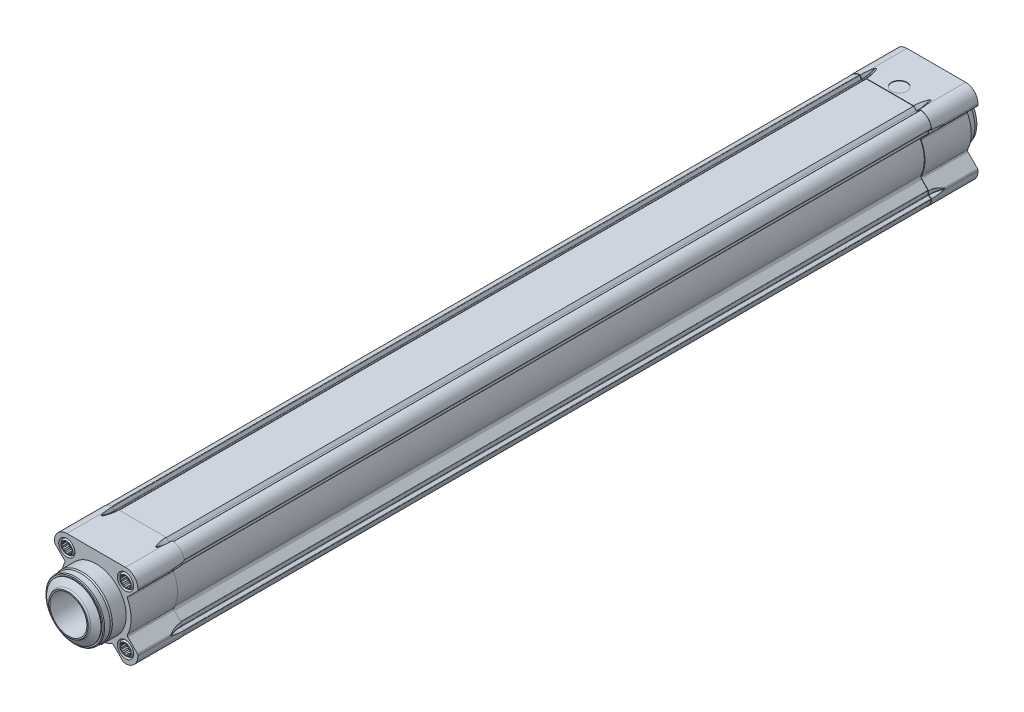
SolidWorks part; units mm, degrees
ref_plane "Front Plane" through (0, 0, 0) normal (0, 0, 1) x (1, 0, 0)
ref_plane "Top Plane" through (0, 0, 0) normal (0, 1, 0) x (1, 0, 0)
ref_plane "Right Plane" through (0, 0, 0) normal (1, 0, 0) x (0, 0, -1)
ref_plane "Plane1" through (0, 0, -30) normal (0, 0, 1) x (1, 0, 0)
sketch "Sketch1" plane through (0, 0, -30) normal (0, 0, 1) x (1, 0, 0)
  line L0 (-26.7071, 17.5147) -> (-20.4561, 11.2637)
  line L1 (-20.4561, -11.2637) -> (-26.7071, -17.5147)
  line L2 (-27, -18.2218) -> (-27, -19)
  line L3 (-19, -27) -> (-18.2218, -27)
  line L4 (-17.5147, -26.7071) -> (-11.2637, -20.4561)
  line L5 (11.2637, -20.4561) -> (17.5147, -26.7071)
  line L6 (18.2218, -27) -> (19, -27)
  line L7 (27, -19) -> (27, -18.2218)
  line L8 (26.7071, -17.5147) -> (20.4561, -11.2637)
  line L9 (20.4561, 11.2637) -> (26.7071, 17.5147)
  line L10 (27, 18.2218) -> (27, 19)
  line L11 (19, 27) -> (-19, 27)
  line L12 (-27, 19) -> (-27, 18.2218)
  arc A0 (-27, 18.2218) -> (-26.7071, 17.5147) centre (-26, 18.2218) ccw
  arc A1 (-20.4561, 11.2637) -> (-20.2683, 10.1102) centre (-21.1632, 10.5566) cw
  arc A2 (-20.2683, 10.1102) -> (-20.2683, -10.1102) centre (0, 0) ccw
  arc A3 (-20.2683, -10.1102) -> (-20.4561, -11.2637) centre (-21.1632, -10.5566) cw
  arc A4 (-26.7071, -17.5147) -> (-27, -18.2218) centre (-26, -18.2218) ccw
  arc A5 (-27, -19) -> (-19, -27) centre (-19, -19) ccw
  arc A6 (-18.2218, -27) -> (-17.5147, -26.7071) centre (-18.2218, -26) ccw
  arc A7 (-11.2637, -20.4561) -> (-10.1102, -20.2683) centre (-10.5566, -21.1632) cw
  arc A8 (-10.1102, -20.2683) -> (10.1102, -20.2683) centre (0, 0) ccw
  arc A9 (10.1102, -20.2683) -> (11.2637, -20.4561) centre (10.5566, -21.1632) cw
  arc A10 (17.5147, -26.7071) -> (18.2218, -27) centre (18.2218, -26) ccw
  arc A11 (19, -27) -> (27, -19) centre (19, -19) ccw
  arc A12 (27, -18.2218) -> (26.7071, -17.5147) centre (26, -18.2218) ccw
  arc A13 (20.4561, -11.2637) -> (20.2683, -10.1102) centre (21.1632, -10.5566) cw
  arc A14 (20.2683, -10.1102) -> (20.2683, 10.1102) centre (0, 0) ccw
  arc A15 (20.2683, 10.1102) -> (20.4561, 11.2637) centre (21.1632, 10.5566) cw
  arc A16 (26.7071, 17.5147) -> (27, 18.2218) centre (26, 18.2218) ccw
  arc A17 (27, 19) -> (19, 27) centre (19, 19) ccw
  arc A18 (-19, 27) -> (-27, 19) centre (-19, 19) ccw
extrude "Boss-Extrude1" add sketch "Sketch1" along normal blind 30
sketch "Sketch2" plane through (0, 0, -30) normal (0, 0, 1) x (1, 0, 0)
  line L0 (-19.3, 33.75) -> (-19.3, 27)
  line L1 (-19.3, 27) -> (-18.203, 25.1)
  line L2 (-18.0298, 25) -> (-17.3281, 25)
  line L3 (-17.1867, 25.0586) -> (-15.2453, 27)
  line L4 (-15.2453, 27) -> (15.2453, 27)
  line L5 (15.2453, 27) -> (17.1867, 25.0586)
  line L6 (17.3281, 25) -> (18.0298, 25)
  line L7 (18.203, 25.1) -> (19.3, 27)
  line L8 (19.3, 27) -> (19.3, 33.75)
  line L9 (19.3, 33.75) -> (-19.3, 33.75)
  line L10 (-50, 45) -> (50, 45) construction
  arc A0 (-18.203, 25.1) -> (-18.0298, 25) centre (-18.0298, 25.2) ccw
  arc A1 (-17.3281, 25) -> (-17.1867, 25.0586) centre (-17.3281, 25.2) ccw
  arc A2 (17.1867, 25.0586) -> (17.3281, 25) centre (17.3281, 25.2) ccw
  arc A3 (18.0298, 25) -> (18.203, 25.1) centre (18.0298, 25.2) ccw
revolve "Cut-Revolve1" cut sketch "Sketch2" angle 360 about L10 reverse direction yes
sketch "Sketch3" plane through (0, 0, -30) normal (0, 0, 1) x (1, 0, 0)
  line L0 (-19.3, -33.75) -> (19.3, -33.75)
  line L1 (19.3, -33.75) -> (19.3, -27)
  line L2 (19.3, -27) -> (18.203, -25.1)
  line L3 (18.0298, -25) -> (5.7378, -25)
  line L4 (-5.7378, -25) -> (-18.0298, -25)
  line L5 (-18.203, -25.1) -> (-19.3, -27)
  line L6 (-19.3, -27) -> (-19.3, -33.75)
  line L7 (50, -45) -> (-50, -45) construction
  arc A0 (18.203, -25.1) -> (18.0298, -25) centre (18.0298, -25.2) ccw
  arc A1 (5.7378, -25) -> (-5.7378, -25) centre (0, 0) cw
  arc A2 (-18.0298, -25) -> (-18.203, -25.1) centre (-18.0298, -25.2) ccw
revolve "Cut-Revolve2" cut sketch "Sketch3" angle 360 about L7 reverse direction yes
sketch "Sketch4" plane through (0, 0, -30) normal (0, 0, 1) x (1, 0, 0)
  line L0 (25, -5.7378) -> (25, -18.0298)
  line L1 (25.1, -18.203) -> (27, -19.3)
  line L2 (27, -19.3) -> (33.75, -19.3)
  line L3 (33.75, -19.3) -> (33.75, 19.3)
  line L4 (33.75, 19.3) -> (27, 19.3)
  line L5 (27, 19.3) -> (25.1, 18.203)
  line L6 (25, 18.0298) -> (25, 5.7378)
  line L7 (45, 50) -> (45, -50) construction
  arc A0 (25, -18.0298) -> (25.1, -18.203) centre (25.2, -18.0298) ccw
  arc A1 (25.1, 18.203) -> (25, 18.0298) centre (25.2, 18.0298) ccw
  arc A2 (25, 5.7378) -> (25, -5.7378) centre (0, 0) cw
revolve "Cut-Revolve3" cut sketch "Sketch4" angle 360 about L7 reverse direction yes
sketch "Sketch5" plane through (0, 0, -30) normal (0, 0, 1) x (1, 0, 0)
  line L0 (-33.75, -19.3) -> (-27, -19.3)
  line L1 (-27, -19.3) -> (-25.1, -18.203)
  line L2 (-25, -18.0298) -> (-25, -5.7378)
  line L3 (-25, 5.7378) -> (-25, 18.0298)
  line L4 (-25.1, 18.203) -> (-27, 19.3)
  line L5 (-27, 19.3) -> (-33.75, 19.3)
  line L6 (-33.75, 19.3) -> (-33.75, -19.3)
  line L7 (-45, -50) -> (-45, 50) construction
  arc A0 (-25.1, -18.203) -> (-25, -18.0298) centre (-25.2, -18.0298) ccw
  arc A1 (-25, -5.7378) -> (-25, 5.7378) centre (0, 0) cw
  arc A2 (-25, 18.0298) -> (-25.1, 18.203) centre (-25.2, 18.0298) ccw
revolve "Cut-Revolve4" cut sketch "Sketch5" angle 360 about L7 reverse direction yes
sketch "Sketch6" plane through (0, 0, 0) normal (1, 0, 0) x (0, 0, -1)
  line L0 (30, 0) -> (30, 5)
  line L1 (30, 5) -> (514, 5)
  line L2 (514, 5) -> (514, 0)
  line L3 (514, 0) -> (30, 0)
  line L4 (514, 0) -> (30, 0) construction
revolve "Revolve1" add sketch "Sketch6" angle 360 about L4 reverse direction yes
ref_plane "Plane2" through (0, 0, -514) normal (0, 0, 1) x (1, 0, 0)
sketch "Sketch7" plane through (0, 0, -514) normal (0, 0, 1) x (1, 0, 0)
  line L0 (-26.7071, 17.5147) -> (-20.4561, 11.2637)
  line L1 (-20.4561, -11.2637) -> (-26.7071, -17.5147)
  line L2 (-27, -18.2218) -> (-27, -19)
  line L3 (-19, -27) -> (-18.2218, -27)
  line L4 (-17.5147, -26.7071) -> (-11.2637, -20.4561)
  line L5 (11.2637, -20.4561) -> (17.5147, -26.7071)
  line L6 (18.2218, -27) -> (19, -27)
  line L7 (27, -19) -> (27, -18.2218)
  line L8 (26.7071, -17.5147) -> (20.4561, -11.2637)
  line L9 (20.4561, 11.2637) -> (26.7071, 17.5147)
  line L10 (27, 18.2218) -> (27, 19)
  line L11 (19, 27) -> (-19, 27)
  line L12 (-27, 19) -> (-27, 18.2218)
  arc A0 (-27, 18.2218) -> (-26.7071, 17.5147) centre (-26, 18.2218) ccw
  arc A1 (-20.4561, 11.2637) -> (-20.2683, 10.1102) centre (-21.1632, 10.5566) cw
  arc A2 (-20.2683, 10.1102) -> (-20.2683, -10.1102) centre (0, 0) ccw
  arc A3 (-20.2683, -10.1102) -> (-20.4561, -11.2637) centre (-21.1632, -10.5566) cw
  arc A4 (-26.7071, -17.5147) -> (-27, -18.2218) centre (-26, -18.2218) ccw
  arc A5 (-27, -19) -> (-19, -27) centre (-19, -19) ccw
  arc A6 (-18.2218, -27) -> (-17.5147, -26.7071) centre (-18.2218, -26) ccw
  arc A7 (-11.2637, -20.4561) -> (-10.1102, -20.2683) centre (-10.5566, -21.1632) cw
  arc A8 (-10.1102, -20.2683) -> (10.1102, -20.2683) centre (0, 0) ccw
  arc A9 (10.1102, -20.2683) -> (11.2637, -20.4561) centre (10.5566, -21.1632) cw
  arc A10 (17.5147, -26.7071) -> (18.2218, -27) centre (18.2218, -26) ccw
  arc A11 (19, -27) -> (27, -19) centre (19, -19) ccw
  arc A12 (27, -18.2218) -> (26.7071, -17.5147) centre (26, -18.2218) ccw
  arc A13 (20.4561, -11.2637) -> (20.2683, -10.1102) centre (21.1632, -10.5566) cw
  arc A14 (20.2683, -10.1102) -> (20.2683, 10.1102) centre (0, 0) ccw
  arc A15 (20.2683, 10.1102) -> (20.4561, 11.2637) centre (21.1632, 10.5566) cw
  arc A16 (26.7071, 17.5147) -> (27, 18.2218) centre (26, 18.2218) ccw
  arc A17 (27, 19) -> (19, 27) centre (19, 19) ccw
  arc A18 (-19, 27) -> (-27, 19) centre (-19, 19) ccw
extrude "Boss-Extrude2" add sketch "Sketch7" against normal blind 30
sketch "Sketch8" plane through (0, 0, -514) normal (0, 0, 1) x (1, 0, 0)
  line L0 (-19.3, 33.75) -> (-19.3, 27)
  line L1 (-19.3, 27) -> (-18.203, 25.1)
  line L2 (-18.0298, 25) -> (-17.3281, 25)
  line L3 (-17.1867, 25.0586) -> (-15.2453, 27)
  line L4 (-15.2453, 27) -> (15.2453, 27)
  line L5 (15.2453, 27) -> (17.1867, 25.0586)
  line L6 (17.3281, 25) -> (18.0298, 25)
  line L7 (18.203, 25.1) -> (19.3, 27)
  line L8 (19.3, 27) -> (19.3, 33.75)
  line L9 (19.3, 33.75) -> (-19.3, 33.75)
  line L10 (-50, 45) -> (50, 45) construction
  arc A0 (-18.203, 25.1) -> (-18.0298, 25) centre (-18.0298, 25.2) ccw
  arc A1 (-17.3281, 25) -> (-17.1867, 25.0586) centre (-17.3281, 25.2) ccw
  arc A2 (17.1867, 25.0586) -> (17.3281, 25) centre (17.3281, 25.2) ccw
  arc A3 (18.0298, 25) -> (18.203, 25.1) centre (18.0298, 25.2) ccw
revolve "Cut-Revolve5" cut sketch "Sketch8" angle 360 about L10 reverse direction yes
sketch "Sketch9" plane through (0, 0, -514) normal (0, 0, 1) x (1, 0, 0)
  line L0 (-19.3, -27) -> (-19.3, -36)
  line L1 (-19.3, -36) -> (19.3, -36)
  line L2 (19.3, -36) -> (19.3, -27)
  line L3 (19.3, -27) -> (18.203, -25.1)
  line L4 (18.0298, -25) -> (5.7378, -25)
  line L5 (-5.7378, -25) -> (-18.0298, -25)
  line L6 (-18.203, -25.1) -> (-19.3, -27)
  line L7 (50, -45) -> (-50, -45) construction
  arc A0 (18.203, -25.1) -> (18.0298, -25) centre (18.0298, -25.2) ccw
  arc A1 (5.7378, -25) -> (-5.7378, -25) centre (0, 0) cw
  arc A2 (-18.0298, -25) -> (-18.203, -25.1) centre (-18.0298, -25.2) ccw
revolve "Cut-Revolve6" cut sketch "Sketch9" angle 360 about L7 reverse direction yes
sketch "Sketch10" plane through (0, 0, -514) normal (0, 0, 1) x (1, 0, 0)
  line L0 (25, -5.7378) -> (25, -18.0298)
  line L1 (25.1, -18.203) -> (27, -19.3)
  line L2 (27, -19.3) -> (33.75, -19.3)
  line L3 (33.75, -19.3) -> (33.75, 19.3)
  line L4 (33.75, 19.3) -> (27, 19.3)
  line L5 (27, 19.3) -> (25.1, 18.203)
  line L6 (25, 18.0298) -> (25, 5.7378)
  line L7 (45, 50) -> (45, -50) construction
  arc A0 (25, -18.0298) -> (25.1, -18.203) centre (25.2, -18.0298) ccw
  arc A1 (25.1, 18.203) -> (25, 18.0298) centre (25.2, 18.0298) ccw
  arc A2 (25, 5.7378) -> (25, -5.7378) centre (0, 0) cw
revolve "Cut-Revolve7" cut sketch "Sketch10" angle 360 about L7 reverse direction yes
sketch "Sketch11" plane through (0, 0, -514) normal (0, 0, 1) x (1, 0, 0)
  line L0 (-33.75, -19.3) -> (-27, -19.3)
  line L1 (-27, -19.3) -> (-25.1, -18.203)
  line L2 (-25, -18.0298) -> (-25, -5.7378)
  line L3 (-25, 5.7378) -> (-25, 18.0298)
  line L4 (-25.1, 18.203) -> (-27, 19.3)
  line L5 (-27, 19.3) -> (-33.75, 19.3)
  line L6 (-33.75, 19.3) -> (-33.75, -19.3)
  line L7 (-45, -50) -> (-45, 50) construction
  arc A0 (-25.1, -18.203) -> (-25, -18.0298) centre (-25.2, -18.0298) ccw
  arc A1 (-25, -5.7378) -> (-25, 5.7378) centre (0, 0) cw
  arc A2 (-25, 18.0298) -> (-25.1, 18.203) centre (-25.2, 18.0298) ccw
revolve "Cut-Revolve8" cut sketch "Sketch11" angle 360 about L7 reverse direction yes
sketch "Sketch12" plane through (0, 0, -30) normal (0, 0, 1) x (1, 0, 0)
  line L0 (-19.5466, -26.5208) -> (-18.582, -24.85)
  line L1 (-18.2356, -24.65) -> (-15.9769, -24.65)
  line L2 (-15.694, -24.5328) -> (-11.6056, -20.4444)
  line L3 (11.6056, -20.4444) -> (15.694, -24.5328)
  line L4 (15.9769, -24.65) -> (18.2356, -24.65)
  line L5 (18.582, -24.85) -> (19.5466, -26.5208)
  line L6 (26.5208, -19.5466) -> (24.85, -18.582)
  line L7 (24.65, -18.2356) -> (24.65, -15.9769)
  line L8 (24.5328, -15.694) -> (20.4444, -11.6056)
  line L9 (19.5191, 10.6803) -> (24.5328, 15.694)
  line L10 (24.65, 15.9769) -> (24.65, 18.2356)
  line L11 (24.85, 18.582) -> (26.5208, 19.5466)
  line L12 (19.5466, 26.5208) -> (18.582, 24.85)
  line L13 (18.2356, 24.65) -> (17.9713, 24.65)
  line L14 (16.9107, 25.0893) -> (15.25, 26.75)
  line L15 (15.25, 26.75) -> (-15.25, 26.75)
  line L16 (-15.25, 26.75) -> (-16.9107, 25.0893)
  line L17 (-17.9713, 24.65) -> (-18.2356, 24.65)
  line L18 (-18.582, 24.85) -> (-19.5466, 26.5208)
  line L19 (-26.5208, 19.5466) -> (-24.85, 18.582)
  line L20 (-24.65, 18.2356) -> (-24.65, 15.9769)
  line L21 (-24.5328, 15.694) -> (-19.5191, 10.6803)
  line L22 (-20.4444, -11.6056) -> (-24.5328, -15.694)
  line L23 (-24.65, -15.9769) -> (-24.65, -18.2356)
  line L24 (-24.85, -18.582) -> (-26.5208, -19.5466)
  arc A0 (-26.5208, -19.5466) -> (-26.7192, -19.9293) centre (-26.3208, -19.893) ccw
  arc A1 (-26.7192, -19.9293) -> (-19.9293, -26.7192) centre (-19.25, -19.25) ccw
  arc A2 (-19.9293, -26.7192) -> (-19.5466, -26.5208) centre (-19.893, -26.3208) ccw
  arc A3 (-18.582, -24.85) -> (-18.2356, -24.65) centre (-18.2356, -25.05) cw
  arc A4 (-15.9769, -24.65) -> (-15.694, -24.5328) centre (-15.9769, -24.25) ccw
  arc A5 (-11.6056, -20.4444) -> (-9.5594, -20.0918) centre (-10.3328, -21.7172) cw
  arc A6 (-9.5594, -20.0918) -> (9.5594, -20.0918) centre (0, 0) ccw
  arc A7 (9.5594, -20.0918) -> (11.6056, -20.4444) centre (10.3328, -21.7172) cw
  arc A8 (15.694, -24.5328) -> (15.9769, -24.65) centre (15.9769, -24.25) ccw
  arc A9 (18.2356, -24.65) -> (18.582, -24.85) centre (18.2356, -25.05) cw
  arc A10 (19.5466, -26.5208) -> (19.9293, -26.7192) centre (19.893, -26.3208) ccw
  arc A11 (19.9293, -26.7192) -> (26.7192, -19.9293) centre (19.25, -19.25) ccw
  arc A12 (26.7192, -19.9293) -> (26.5208, -19.5466) centre (26.3208, -19.893) ccw
  arc A13 (24.85, -18.582) -> (24.65, -18.2356) centre (25.05, -18.2356) cw
  arc A14 (24.65, -15.9769) -> (24.5328, -15.694) centre (24.25, -15.9769) ccw
  arc A15 (20.4444, -11.6056) -> (20.0918, -9.5594) centre (21.7172, -10.3328) cw
  arc A16 (20.0918, -9.5594) -> (19.5191, 10.6803) centre (0, 0) ccw
  arc A17 (24.5328, 15.694) -> (24.65, 15.9769) centre (24.25, 15.9769) ccw
  arc A18 (24.65, 18.2356) -> (24.85, 18.582) centre (25.05, 18.2356) cw
  arc A19 (26.5208, 19.5466) -> (26.7192, 19.9293) centre (26.3208, 19.893) ccw
  arc A20 (26.7192, 19.9293) -> (19.9293, 26.7192) centre (19.25, 19.25) ccw
  arc A21 (19.9293, 26.7192) -> (19.5466, 26.5208) centre (19.893, 26.3208) ccw
  arc A22 (18.582, 24.85) -> (18.2356, 24.65) centre (18.2356, 25.05) cw
  arc A23 (17.9713, 24.65) -> (16.9107, 25.0893) centre (17.9713, 26.15) cw
  arc A24 (-16.9107, 25.0893) -> (-17.9713, 24.65) centre (-17.9713, 26.15) cw
  arc A25 (-18.2356, 24.65) -> (-18.582, 24.85) centre (-18.2356, 25.05) cw
  arc A26 (-19.5466, 26.5208) -> (-19.9293, 26.7192) centre (-19.893, 26.3208) ccw
  arc A27 (-19.9293, 26.7192) -> (-26.7192, 19.9293) centre (-19.25, 19.25) ccw
  arc A28 (-26.7192, 19.9293) -> (-26.5208, 19.5466) centre (-26.3208, 19.893) ccw
  arc A29 (-24.85, 18.582) -> (-24.65, 18.2356) centre (-25.05, 18.2356) cw
  arc A30 (-24.65, 15.9769) -> (-24.5328, 15.694) centre (-24.25, 15.9769) ccw
  arc A31 (-19.5191, 10.6803) -> (-20.0918, -9.5594) centre (0, 0) ccw
  arc A32 (-20.0918, -9.5594) -> (-20.4444, -11.6056) centre (-21.7172, -10.3328) cw
  arc A33 (-24.5328, -15.694) -> (-24.65, -15.9769) centre (-24.25, -15.9769) ccw
  arc A34 (-24.65, -18.2356) -> (-24.85, -18.582) centre (-25.05, -18.2356) cw
extrude "Boss-Extrude3" add sketch "Sketch12" against normal blind 484
sketch "Sketch13" plane through (0, 0, 0) normal (1, 0, 0) x (0, 0, -1)
  line L0 (-18, 0) -> (-18, 12.75)
  line L1 (-16.8683, 13.4103) -> (-14.5, 17.6)
  line L2 (-14.5, 17.6) -> (-14, 17.6)
  line L3 (-14, 17.6) -> (-14, 18.5)
  line L4 (-14, 18.5) -> (-13.5, 19)
  line L5 (-13.5, 19) -> (-9.866, 19)
  line L6 (-9.866, 19) -> (-9, 19.5)
  line L7 (-9, 19.5) -> (0, 19.5)
  line L8 (0, 19.5) -> (0, 0)
  line L9 (0, 0) -> (-18, 0)
  line L10 (0, 0) -> (-18, 0) construction
  arc A0 (-18, 12.75) -> (-16.8683, 13.4103) centre (-18, 14.05) ccw
revolve "Revolve2" add sketch "Sketch13" angle 360 about L10 reverse direction yes
ref_plane "Plane3" through (0, 0, -520) normal (0, 0, 1) x (1, 0, 0)
sketch "Sketch14" plane through (0, 0, -520) normal (0, 0, 1) x (1, 0, 0)
  line L0 (0, 27) -> (5, 27)
  line L1 (5, 27) -> (5, 26.7)
  line L2 (5, 26.7) -> (0, 26.7)
  line L3 (0, 26.7) -> (0, 27)
  line L4 (0, 26.7) -> (0, 27) construction
revolve "Cut-Revolve9" cut sketch "Sketch14" angle 360 about L4 reverse direction yes
ref_plane "Plane4" through (0, 27, 0) normal (0, 1, 0) x (1, 0, 0)
ref_plane "Plane5" through (19, 0, 0) normal (1, 0, 0) x (0, 0, -1)
sketch "Sketch15" plane through (19, 0, 0) normal (1, 0, 0) x (0, 0, -1)
  line L0 (0, 19) -> (0, 24.25)
  line L1 (0, 24.25) -> (21.1, 24.25)
  line L2 (21.1, 24.25) -> (21.1, 19)
  line L3 (21.1, 19) -> (0, 19)
  line L4 (21.1, 19) -> (0, 19) construction
revolve "Cut-Revolve10" cut sketch "Sketch15" angle 360 about L4 reverse direction yes
sketch "Sketch16" plane through (0, 0, 0) normal (0, 0, 1) x (1, 0, 0)
  line L0 (19, 19) -> (-19, 19)
  line L1 (19, 19) -> (19, -19)
pattern_linear "LPattern1" count 2 spacing 38 along (-1, 0, 0) count 2 spacing 38 along (0, -1, 0) of "Cut-Revolve10"
sketch "Sketch17" plane through (19, 0, 0) normal (1, 0, 0) x (0, 0, -1)
  line L0 (0, 19) -> (0, 22.6609)
  line L1 (0, 22.6609) -> (1, 23.5)
  line L2 (1, 23.5) -> (21.1, 23.5)
  line L3 (21.1, 23.5) -> (21.1, 19)
  line L4 (21.1, 19) -> (0, 19)
  line L5 (21.1, 19) -> (0, 19) construction
revolve "Revolve3" add sketch "Sketch17" angle 360 about L5 reverse direction yes
sketch "Sketch18" plane through (0, 0, 0) normal (0, 0, 1) x (1, 0, 0)
  line L0 (19, 19) -> (-19, 19)
  line L1 (19, 19) -> (19, -19)
pattern_linear "LPattern2" count 2 spacing 38 along (-1, 0, 0) count 2 spacing 38 along (0, -1, 0) of "Revolve3"
sketch "Sketch19" plane through (19, 0, 0) normal (1, 0, 0) x (0, 0, -1)
  line L0 (0, 19) -> (0, 22.5)
  line L1 (0, 22.5) -> (0.2887, 22)
  line L2 (0.2887, 22) -> (5.5, 22)
  line L3 (5.5, 22) -> (6.0415, 21.4585)
  line L4 (6.0415, 21.4585) -> (18.7, 21.4585)
  line L5 (18.7, 21.4585) -> (20.1194, 19)
  line L6 (20.1194, 19) -> (0, 19)
  line L7 (20.1194, 19) -> (0, 19) construction
revolve "Cut-Revolve11" cut sketch "Sketch19" angle 360 about L7 reverse direction yes
cosmetic thread "Cosmetic Thread1" parameters "D1"=10.5, "D2"=6
sketch "Sketch20" plane through (0, 0, 0) normal (0, 0, 1) x (1, 0, 0)
  line L0 (15.5359, 19) -> (16, 18.1962)
  line L1 (16, 18.1962) -> (16, 17.2679)
  line L2 (16, 17.2679) -> (16.8038, 16.8038)
  line L3 (16.8038, 16.8038) -> (17.2679, 16)
  line L4 (17.2679, 16) -> (18.1962, 16)
  line L5 (18.1962, 16) -> (19, 15.5359)
  line L6 (19, 15.5359) -> (19.8038, 16)
  line L7 (19.8038, 16) -> (20.7321, 16)
  line L8 (20.7321, 16) -> (21.1962, 16.8038)
  line L9 (21.1962, 16.8038) -> (22, 17.2679)
  line L10 (22, 17.2679) -> (22, 18.1962)
  line L11 (22, 18.1962) -> (22.4641, 19)
  line L12 (22.4641, 19) -> (22, 19.8038)
  line L13 (22, 19.8038) -> (22, 20.7321)
  line L14 (22, 20.7321) -> (21.1962, 21.1962)
  line L15 (21.1962, 21.1962) -> (20.7321, 22)
  line L16 (20.7321, 22) -> (19.8038, 22)
  line L17 (19.8038, 22) -> (19, 22.4641)
  line L18 (19, 22.4641) -> (18.1962, 22)
  line L19 (18.1962, 22) -> (17.2679, 22)
  line L20 (17.2679, 22) -> (16.8038, 21.1962)
  line L21 (16.8038, 21.1962) -> (16, 20.7321)
  line L22 (16, 20.7321) -> (16, 19.8038)
  line L23 (16, 19.8038) -> (15.5359, 19)
extrude "Cut-Extrude1" cut sketch "Sketch20" along normal blind 4 and the other way blind 4
sketch "Sketch21" plane through (0, 0, 0) normal (0, 0, 1) x (1, 0, 0)
  line L0 (19, 19) -> (-19, 19)
  line L1 (19, 19) -> (19, -19)
pattern_linear "LPattern3" count 2 spacing 38 along (-1, 0, 0) count 2 spacing 38 along (0, -1, 0) of "Cut-Revolve11"
cosmetic thread "Cosmetic Thread2" parameters "D1"=10.5, "D2"=6
cosmetic thread "Cosmetic Thread3" parameters "D1"=10.5, "D2"=6
cosmetic thread "Cosmetic Thread4" parameters "D1"=10.5, "D2"=6
sketch "Sketch22" plane through (0, 0, 0) normal (0, 0, 1) x (1, 0, 0)
  line L0 (19, 19) -> (-19, 19)
  line L1 (19, 19) -> (19, -19)
pattern_linear "LPattern4" count 2 spacing 38 along (-1, 0, 0) count 2 spacing 38 along (0, -1, 0) of "Cut-Extrude1"
ref_plane "Plane6" through (0, 0, -544) normal (0, 0, 1) x (1, 0, 0)
sketch "Sketch23" plane through (0, 0, 0) normal (1, 0, 0) x (0, 0, -1)
  line L0 (544, 0) -> (544, 20)
  line L1 (544, 20) -> (549, 20)
  line L2 (549, 20) -> (551, 19.2721)
  line L3 (551, 19.2721) -> (551, 0)
  line L4 (551, 0) -> (544, 0)
  line L5 (551, 0) -> (544, 0) construction
revolve "Revolve4" add sketch "Sketch23" angle 360 about L5 reverse direction yes
sketch "Sketch24" plane through (0, 0, 0) normal (1, 0, 0) x (0, 0, -1)
  line L0 (514, 0) -> (514, 5)
  line L1 (514, 5) -> (540.8, 5)
  line L2 (540.8, 5) -> (540.8, 16.5)
  line L3 (540.8, 16.5) -> (550, 16.5)
  line L4 (550, 16.5) -> (551, 16.864)
  line L5 (551, 16.864) -> (551, 0)
  line L6 (551, 0) -> (514, 0)
  line L7 (551, 0) -> (514, 0) construction
revolve "Cut-Revolve12" cut sketch "Sketch24" angle 360 about L7 reverse direction yes
ref_plane "Plane7" through (0, 0, 0) normal (1, 0, 0) x (0, 0, -1)
sketch "Sketch25" plane through (19, 0, 0) normal (1, 0, 0) x (0, 0, -1)
  line L0 (522.9, 19) -> (522.9, 24.25)
  line L1 (522.9, 24.25) -> (544, 24.25)
  line L2 (544, 24.25) -> (544, 19)
  line L3 (544, 19) -> (522.9, 19)
  line L4 (544, 19) -> (522.9, 19) construction
revolve "Cut-Revolve13" cut sketch "Sketch25" angle 360 about L4 reverse direction yes
sketch "Sketch26" plane through (0, 0, -544) normal (0, 0, 1) x (1, 0, 0)
  line L0 (19, 19) -> (-19, 19)
  line L1 (19, 19) -> (19, -19)
pattern_linear "LPattern5" count 2 spacing 38 along (-1, 0, 0) count 2 spacing 38 along (0, -1, 0) of "Cut-Revolve13"
sketch "Sketch27" plane through (19, 0, 0) normal (1, 0, 0) x (0, 0, -1)
  line L0 (522.9, 19) -> (522.9, 23.5)
  line L1 (522.9, 23.5) -> (543, 23.5)
  line L2 (543, 23.5) -> (544, 22.6609)
  line L3 (544, 22.6609) -> (544, 19)
  line L4 (544, 19) -> (522.9, 19)
  line L5 (544, 19) -> (522.9, 19) construction
revolve "Revolve5" add sketch "Sketch27" angle 360 about L5 reverse direction yes
sketch "Sketch28" plane through (0, 0, -544) normal (0, 0, 1) x (1, 0, 0)
  line L0 (19, 19) -> (-19, 19)
  line L1 (19, 19) -> (19, -19)
pattern_linear "LPattern6" count 2 spacing 38 along (-1, 0, 0) count 2 spacing 38 along (0, -1, 0) of "Revolve5"
sketch "Sketch29" plane through (19, 0, 0) normal (1, 0, 0) x (0, 0, -1)
  line L0 (523.8806, 19) -> (525.3, 21.4585)
  line L1 (525.3, 21.4585) -> (537.9585, 21.4585)
  line L2 (537.9585, 21.4585) -> (538.5, 22)
  line L3 (538.5, 22) -> (543.7113, 22)
  line L4 (543.7113, 22) -> (544, 22.5)
  line L5 (544, 22.5) -> (544, 19)
  line L6 (544, 19) -> (523.8806, 19)
  line L7 (544, 19) -> (523.8806, 19) construction
revolve "Cut-Revolve14" cut sketch "Sketch29" angle 360 about L7 reverse direction yes
cosmetic thread "Cosmetic Thread5" parameters "D1"=10.5, "D2"=6
sketch "Sketch30" plane through (0, 0, -544) normal (0, 0, 1) x (1, 0, 0)
  line L0 (19, 19) -> (-19, 19)
  line L1 (19, 19) -> (19, -19)
pattern_linear "LPattern7" count 2 spacing 38 along (-1, 0, 0) count 2 spacing 38 along (0, -1, 0) of "Cut-Revolve14"
cosmetic thread "Cosmetic Thread6" parameters "D1"=10.5, "D2"=6
cosmetic thread "Cosmetic Thread7" parameters "D1"=10.5, "D2"=6
cosmetic thread "Cosmetic Thread8" parameters "D1"=10.5, "D2"=6
sketch "Sketch31" plane through (0, 0, -544) normal (0, 0, 1) x (1, 0, 0)
  line L0 (15.5359, 19) -> (16, 18.1962)
  line L1 (16, 18.1962) -> (16, 17.2679)
  line L2 (16, 17.2679) -> (16.8038, 16.8038)
  line L3 (16.8038, 16.8038) -> (17.2679, 16)
  line L4 (17.2679, 16) -> (18.1962, 16)
  line L5 (18.1962, 16) -> (19, 15.5359)
  line L6 (19, 15.5359) -> (19.8038, 16)
  line L7 (19.8038, 16) -> (20.7321, 16)
  line L8 (20.7321, 16) -> (21.1962, 16.8038)
  line L9 (21.1962, 16.8038) -> (22, 17.2679)
  line L10 (22, 17.2679) -> (22, 18.1962)
  line L11 (22, 18.1962) -> (22.4641, 19)
  line L12 (22.4641, 19) -> (22, 19.8038)
  line L13 (22, 19.8038) -> (22, 20.7321)
  line L14 (22, 20.7321) -> (21.1962, 21.1962)
  line L15 (21.1962, 21.1962) -> (20.7321, 22)
  line L16 (20.7321, 22) -> (19.8038, 22)
  line L17 (19.8038, 22) -> (19, 22.4641)
  line L18 (19, 22.4641) -> (18.1962, 22)
  line L19 (18.1962, 22) -> (17.2679, 22)
  line L20 (17.2679, 22) -> (16.8038, 21.1962)
  line L21 (16.8038, 21.1962) -> (16, 20.7321)
  line L22 (16, 20.7321) -> (16, 19.8038)
  line L23 (16, 19.8038) -> (15.5359, 19)
extrude "Cut-Extrude2" cut sketch "Sketch31" along normal blind 4 and the other way blind 4
sketch "Sketch32" plane through (0, 0, -544) normal (0, 0, 1) x (1, 0, 0)
  line L0 (19, 19) -> (-19, 19)
  line L1 (19, 19) -> (19, -19)
pattern_linear "LPattern8" count 2 spacing 38 along (-1, 0, 0) count 2 spacing 38 along (0, -1, 0) of "Cut-Extrude2"
ref_plane "Plane8" through (0, 0, -514) normal (0, 0, 1) x (1, 0, 0)
sketch "Sketch33" plane through (0, 0, 0) normal (1, 0, 0) x (0, 0, -1)
  line L0 (-18, 0) -> (-18, 12)
  line L1 (-18, 12) -> (100.6667, 12)
  line L2 (100.6667, 12) -> (100.6667, 20)
  line L3 (100.6667, 20) -> (514, 20)
  line L4 (514, 20) -> (514, 0)
  line L5 (514, 0) -> (-18, 0)
  line L6 (514, 0) -> (-18, 0) construction
revolve "Cut-Revolve15" cut sketch "Sketch33" angle 360 about L6 reverse direction yes
ref_plane "Plane9" through (0, 0, -272) normal (0, 0, 1) x (1, 0, 0)
ref_plane "GUA XY" through (0, 0, -540.8) normal (0, 0, 1) x (1, 0, 0)
ref_plane "GUA XZ" through (0, 0, 0) normal (1, 0, 0) x (0, 0, -1)
ref_plane "GUA YZ" through (0, 0, 0) normal (0, 1, 0) x (1, 0, 0)
ref_axis "GUA X" through (0, -50, -540.8) along (0, 1, 0)
ref_axis "GUA Y" through (80.9, 0, -540.8) along (-1, 0, 0)
ref_axis "GUA Z" through (0, 0, 50) along (0, 0, -1)
sketch3d "GUA"
  point P0 (0, 0, -540.8)
ref_plane "KS XY" through (0, 0, -514) normal (0, 0, 1) x (1, 0, 0)
ref_plane "KS XZ" through (0, 0, 0) normal (0, -1, 0) x (-1, 0, 0)
ref_plane "KS YZ" through (0, 0, 0) normal (1, 0, 0) x (0, 0, -1)
ref_axis "KS X" through (-80.9, 0, -514) along (1, 0, 0)
ref_axis "KS Y" through (0, -50, -514) along (0, 1, 0)
ref_axis "KS Z" through (0, 0, 80.9) along (0, 0, -1)
sketch3d "KS"
  point P0 (0, 0, -514)
ref_plane "KSA XY" through (0, 0, -514) normal (0, 0, -1) x (-1, 0, 0)
ref_plane "KSA XZ" through (0, 0, 0) normal (0, 1, 0) x (1, 0, 0)
ref_plane "KSA YZ" through (0, 0, 0) normal (1, 0, 0) x (0, 0, -1)
ref_axis "KSA X" through (-80.9, 0, -514) along (1, 0, 0)
ref_axis "KSA Y" through (0, 50, -514) along (0, -1, 0)
ref_axis "KSA Z" through (0, 0, -80.9) along (0, 0, 1)
sketch3d "KSA"
  point P0 (0, 0, -514)
ref_plane "PLUG XY" through (0, 27, 0) normal (0, -1, 0) x (-1, 0, 0)
ref_plane "PLUG XZ" through (0, 0, -520) normal (0, 0, -1) x (-1, 0, 0)
ref_plane "PLUG YZ" through (0, 0, 0) normal (1, 0, 0) x (0, 0, -1)
ref_axis "PLUG X" through (-80.9, 27, -520) along (1, 0, 0)
ref_axis "PLUG Y" through (0, 27, -50) along (0, 0, 1)
ref_axis "PLUG Z" through (0, -50, -520) along (0, 1, 0)
sketch3d "PLUG"
  point P0 (0, 27, -520)
ref_plane "SENSOR XY" through (0, 0, -272) normal (0, 0, 1) x (1, 0, 0)
ref_plane "SENSOR XZ" through (0, 27, 0) normal (0, -1, 0) x (-1, 0, 0)
ref_plane "SENSOR YZ" through (0, 0, 0) normal (1, 0, 0) x (0, 0, -1)
ref_axis "SENSOR X" through (-80.9, 27, -272) along (1, 0, 0)
ref_axis "SENSOR Y" through (0, -50, -272) along (0, 1, 0)
ref_axis "SENSOR Z" through (0, 27, 80.9) along (0, 0, -1)
sketch3d "SENSOR"
  point P0 (0, 27, -272)
ref_plane "START XY" through (0, 0, 0) normal (0, 0, -1) x (-1, 0, 0)
ref_plane "START XZ" through (0, 0, 0) normal (0, 1, 0) x (1, 0, 0)
ref_plane "START YZ" through (0, 0, 0) normal (1, 0, 0) x (0, 0, -1)
ref_axis "START X" through (-80.9, 0, 0) along (1, 0, 0)
ref_axis "START Y" through (0, 50, 0) along (0, -1, 0)
ref_axis "START Z" through (0, 0, -80.9) along (0, 0, 1)
sketch3d "START"
  point P0 (0, 0, 0)
other "Freeze***"
